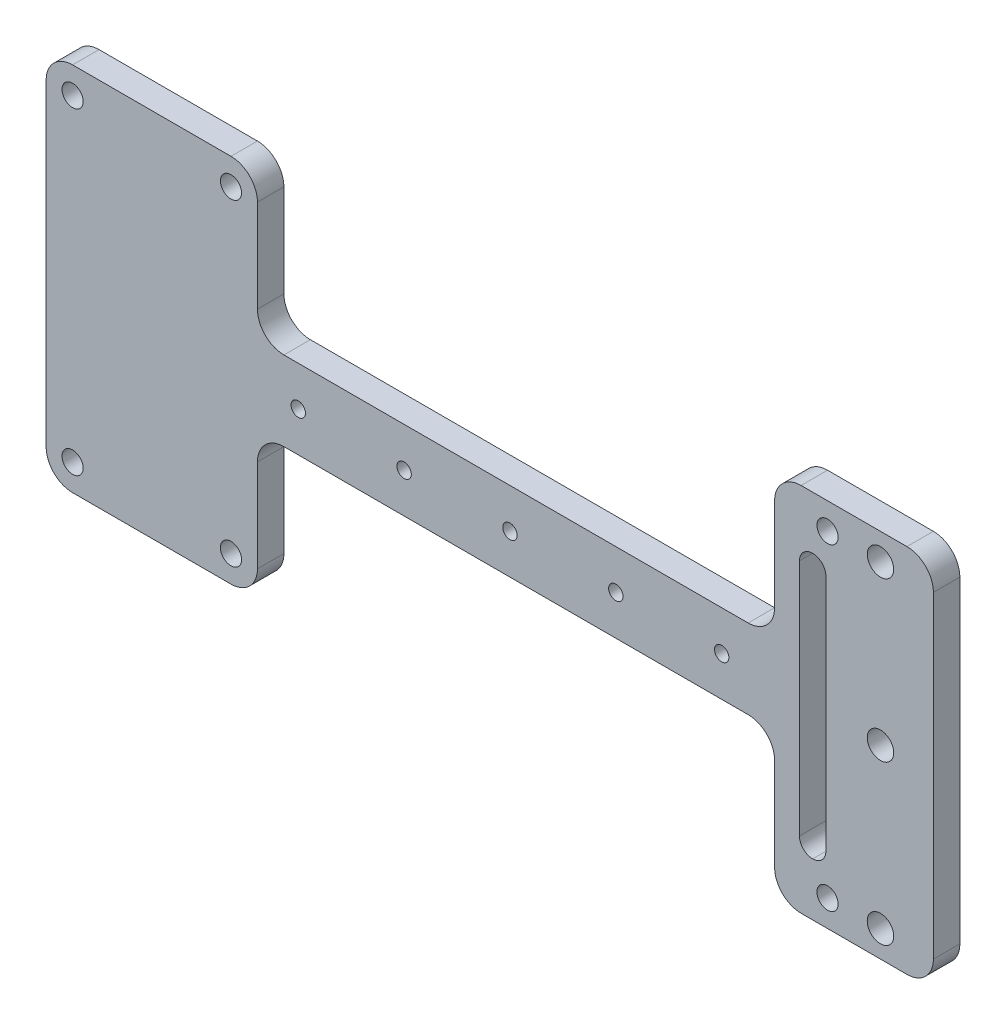
SolidWorks part; units mm, degrees
ref_plane "Front Plane" through (0, 0, 0) normal (0, 0, 1) x (1, 0, 0)
ref_plane "Top Plane" through (0, 0, 0) normal (0, 1, 0) x (1, 0, 0)
ref_plane "Right Plane" through (0, 0, 0) normal (1, 0, 0) x (0, 0, -1)
sketch "Sketch4" plane through (0, 0, 0) normal (0, 0, 1) x (1, 0, 0)
  line L6 (-68, -87) -> (68, -87) construction
  line L7 (-68, -87) -> (-68, 87) construction
  line L8 (68, -87) -> (68, 87) construction
  line L9 (-68, 87) -> (68, 87) construction
  line L10 (-68, -87) -> (68, 87) construction
  line L11 (68, -87) -> (-68, 87) construction
  line L21 (84.2719, 38.1) -> (-109.5719, 38.1) construction
  line L22 (0, -120.1984) -> (0, 120.1984) construction
  line L23 (84.2719, 0) -> (84.2719, 38.1) construction
  line L25 (-102.0926, 0) -> (84.2719, 0) construction
  line L29 (-106, 87) -> (-106, -87) construction
  line L30 (58.8719, 44.45) -> (96.9719, 44.45)
  line L31 (96.9719, 44.45) -> (96.9719, -44.45)
  line L33 (-115.9219, -44.45) -> (-115.9219, 44.45)
  line L34 (-115.9219, 44.45) -> (-65.2219, 44.45)
  line L35 (-65.2219, 44.45) -> (-65.2219, 9.525)
  line L36 (-65.2219, 9.525) -> (58.8719, 9.525)
  line L37 (58.8719, 9.525) -> (58.8719, 44.45)
  line L38 (84.2719, 0) -> (150.1905, 0) construction
  line L39 (58.8719, -44.45) -> (96.9719, -44.45)
  line L40 (58.8719, -9.525) -> (58.8719, -44.45)
  line L41 (-65.2219, -9.525) -> (58.8719, -9.525)
  line L42 (-65.2219, -44.45) -> (-65.2219, -9.525)
  line L43 (-115.9219, -44.45) -> (-65.2219, -44.45)
  line L44 (64.825, 31.75) -> (64.825, -31.75)
  line L45 (64.825, 31.75) -> (71.175, 31.75)
  line L46 (64.825, -31.75) -> (71.175, -31.75)
  line L47 (71.175, 31.75) -> (71.175, -31.75)
  line L48 (64.825, 31.75) -> (71.175, -31.75) construction
  line L49 (64.825, -31.75) -> (71.175, 31.75) construction
  circle A0 centre (-109.5719, 38.1) radius 2.54
  circle A4 centre (84.2719, 38.1) radius 3.175
  circle A8 centre (46.1719, 0) radius 1.7272
  circle A9 centre (20.7719, 0) radius 1.7272
  circle A10 centre (-4.6281, 0) radius 1.7272
  circle A11 centre (-30.0281, 0) radius 1.7272
  circle A14 centre (84.2719, 38.1) radius 4.7625 construction
  circle A15 centre (71.5719, 38.1) radius 2.54
  circle A16 centre (-71.5719, 38.1) radius 2.54
  circle A17 centre (84.2719, -38.1) radius 3.175
  circle A18 centre (71.5719, -38.1) radius 2.54
  circle A19 centre (-71.5719, -38.1) radius 2.54
  circle A20 centre (-109.5719, -38.1) radius 2.54
  circle A21 centre (84.2719, 0) radius 3.175
  circle A22 centre (-55.4281, 0) radius 1.7272
  point P0 (0, 0)
  point P1 (0, 0)
  point P15 (0, 0)
  point P44 (96.9719, 0)
  point P53 (-115.9219, 0)
  point P55 (68, 0)
  dimension "D5" = 5.08
  dimension "D10" = 3.5719
  dimension "D11" = 6.35
  dimension "D18" = 3.4544
  dimension "D19" = 6.35
  dimension "D6" = 38.1
  dimension "D2" = 12.7
  dimension "D3" = 174
  dimension "D4" = 136
  dimension "D7" = 174
  dimension "D8" = 3.5719
  dimension "D9" = 3.5719
  dimension "D12" = 12.7
  dimension "D13" = 12.7
  dimension "D14" = 25.4
  dimension "D15" = 25.4
  dimension "D16" = 38.1
  dimension "D17" = 25.4
  dimension "D20" = 6.35
  dimension "D21" = 6.35
  dimension "D22" = 9.525
  dimension "D23" = 6.35
  dimension "D24" = 63.5
  dimension "D25" = 25.4
extrude "Boss-Extrude4" add sketch "Sketch4" along normal blind 6.35
fillet "Fillet1" radius 6.35 12 edges at (-115.9219, 44.45, 3.175) (-65.2219, 44.45, 3.175) (-65.2219, 9.525, 3.175) (-115.9219, -44.45, 3.175) (-65.2219, -44.45, 3.175) (-65.2219, -9.525, 3.175) (58.8719, -9.525, 3.175) (58.8719, 9.525, 3.175) (58.8719, 44.45, 3.175) (96.9719, 44.45, 3.175) (58.8719, -44.45, 3.175) (96.9719, -44.45, 3.175)
fillet "Fillet2" radius 3.175 4 edges at (71.175, 31.75, 3.175) (64.825, 31.75, 3.175) (71.175, -31.75, 3.175) (64.825, -31.75, 3.175)
sketch "Sketch1" plane through (0, 0, 0) normal (0, 0, 1) x (1, 0, 0)
  line L0 (-68, -87) -> (68, -87)
  line L1 (-68, -87) -> (-68, 87)
  line L2 (68, -87) -> (68, 87)
  line L3 (-68, 87) -> (68, 87)
  line L4 (-68, -87) -> (68, 87) construction
  line L5 (68, -87) -> (-68, 87) construction
  point P1 (0, 0)
  dimension "D1" = 136
  dimension "D2" = 174
sketch "Sketch2" plane through (0, 0, 0) normal (0, 0, 1) x (1, 0, 0)
  line L0 (-64.5, -84.25) -> (59.5, -84.25)
  line L1 (-64.5, -84.25) -> (-64.5, 80.75)
  line L2 (59.5, -84.25) -> (59.5, 80.75)
  line L3 (-64.5, 80.75) -> (59.5, 80.75)
  line L4 (-64.5, -84.25) -> (59.5, 80.75) construction
  line L5 (59.5, -84.25) -> (-64.5, 80.75) construction
  line L10 (-68, 87) -> (68, 87) construction
  line L11 (68, -87) -> (68, 87) construction
  point P1 (-2.5, -1.75)
  dimension "D1" = 124
  dimension "D2" = 165
  dimension "D3" = 8.5
  dimension "D4" = 6.25
sketch "Sketch3" plane through (0, 0, 0) normal (0, 0, 1) x (1, 0, 0)
  line L0 (68, 14.75) -> (68, -17)
  line L1 (68, 14.75) -> (48, 14.75)
  line L2 (68, -17) -> (48, -17)
  line L3 (48, 14.75) -> (48, -17)
  line L6 (-68, 87) -> (68, 87) construction
  line L7 (68, -87) -> (68, 87) construction
  dimension "D1" = 31.75
  dimension "D2" = 72.25
  dimension "D3" = 20
